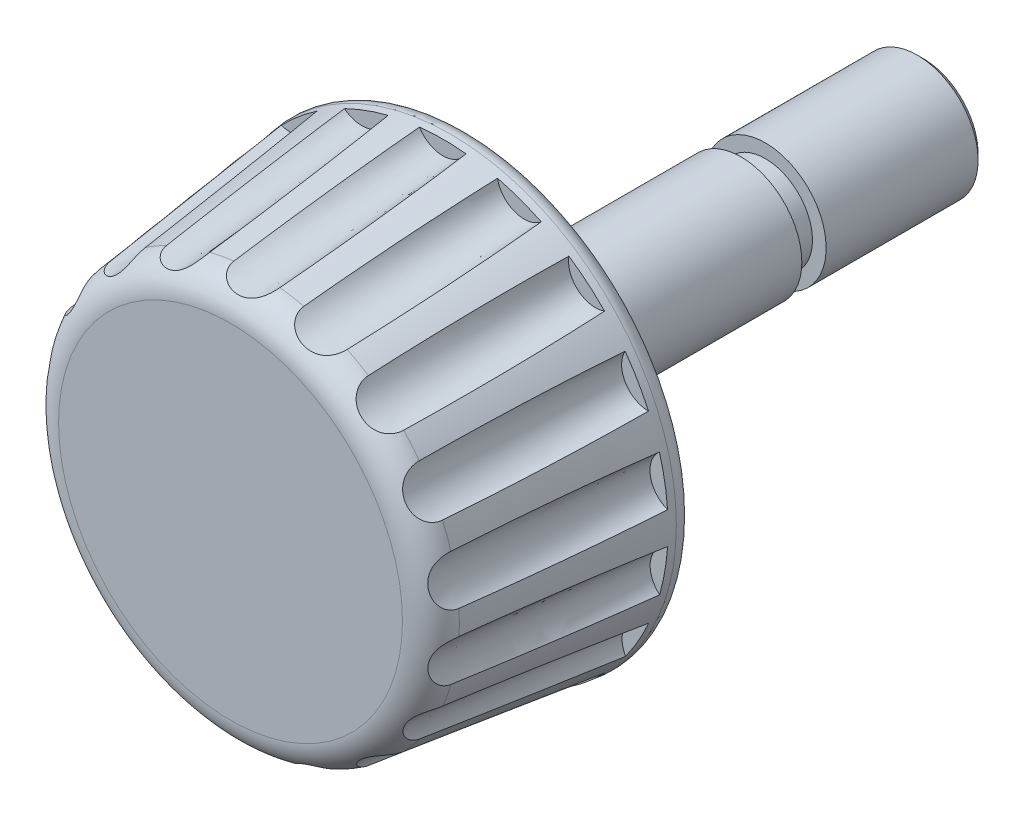
SolidWorks part; units mm, degrees
note: '?' marks a value the reader was unsure of.
ref_plane "Face" through (0, 0, 0) normal (0, 0, 1) x (1, 0, 0)
ref_plane "Dessus" through (0, 0, 0) normal (0, 1, 0) x (1, 0, 0)
ref_plane "Droite" through (0, 0, 0) normal (1, 0, 0) x (0, 0, -1)
sketch "Esquisse1" plane through (0, 0, 0) normal (0, 0, 1) x (1, 0, 0)
  line L0 (-7.5898, 0) -> (8.0648, 0) construction
  line L1 (0, 7.5618) -> (0, -7.1963) construction
  circle A0 centre (0, 0) radius 7.5
extrude "Extrusion1" add sketch "Esquisse1" along normal blind 7.8 draft 7
sketch "Esquisse3" plane through (0, 0, 0) normal (0, 0, -1) x (-1, 0, 0)
  circle A0 centre (0, 0) radius 2
extrude "Extrusion3" add sketch "Esquisse3" along normal blind 15
chamfer "Chanfrein2" distance 0.2 angle 45
fillet "Congé1" radius 1
sketch "Esquisse7" plane through (0, 0, 7.8) normal (0, 0, 1) x (1, 0, 0)
  line L0 (-0.0137, 7.5189) -> (-0.0137, -5.0126) construction
  circle A0 centre (-0.0137, 7.8109) radius 1.5
  dimension "D1" = 3
extrude "Enlèv. mat.-Extru.4" cut sketch "Esquisse7" against normal blind 7 draft 5
ref_axis "Axe1" through (0, 0, -15.57) along (0, 0, 1)?
pattern_circular "Répétition circulaire1" count 18 every 20 about axis through (0, 0, -15.57) along (0, 0, 1)
sketch "Esquisse10" plane through (0, 0, 0) normal (0, 1, 0) x (1, 0, 0)
  line L1 (-2.6086, 9.8) -> (-1.55, 9.8)
  line L2 (-2.6086, 9.8) -> (-2.6086, 9)
  line L3 (-2.6086, 9) -> (-1.55, 9)
  line L4 (-1.55, 9.8) -> (-1.55, 9)
  line L6 (0, 15.4647) -> (0, 1.703) construction
  dimension "D1" = 0.8
  dimension "D3" = 1.55
revolve "Enlèvement de matière-Révolution1" cut sketch "Esquisse10" angle 360 about L6
fillet "Congé2" radius 0.5
